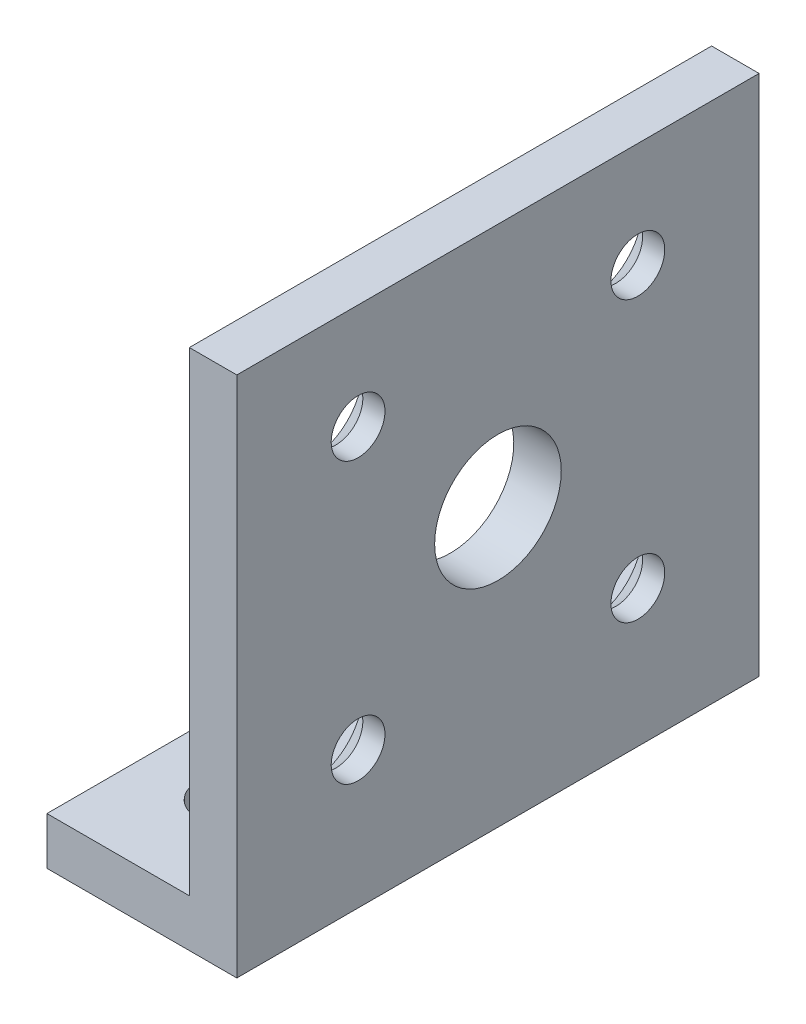
SolidWorks part; units mm, degrees
material "1060 合金"
ref_plane "前视基准面" through (0, 0, 0) normal (0, 0, 1) x (1, 0, 0)
ref_plane "上视基准面" through (0, 0, 0) normal (0, 1, 0) x (1, 0, 0)
ref_plane "右视基准面" through (0, 0, 0) normal (1, 0, 0) x (0, 0, -1)
sketch "草图1" plane through (0, 0, 0) normal (0, 0, 1) x (1, 0, 0)
  line L0 (0, 33) -> (0, 0)
  line L1 (0, 0) -> (-12, 0)
  dimension "D1" = 12
  dimension "D2" = 33
extrude "拉伸-薄壁1" add sketch "草图1" along normal mid plane 33 thin thin type one direction wall 3
sketch "草图4" plane through (-3, 0, 0) normal (-1, 0, 0) x (0, 0, 1)
  line L14 (16.5, 0) -> (-16.5, 0) construction
  line L15 (16.5, 0) -> (-16.5, 0) construction
  circle A0 centre (0, 17.5) radius 16.5 construction
  circle A1 centre (0, 17.5) radius 4
  dimension "D1" = 33
  dimension "D2" = 8
  dimension "D3" = 1
extrude "切除-拉伸1" cut sketch "草图4" against normal up to next
hole_wizard "打孔尺寸(%根据十字)槽半沉头木螺钉的类型2" positions "草图3" profile "草图2" countersink size "M3" standard "GB"
sketch "草图3" plane through (-3, 0, 0) normal (-1, 0, 0) x (0, 0, 1)
  line L1 (0, 17.5) -> (8.8388, 8.6612) construction
  line L3 (0, 17.5) -> (5.8968, 17.5) construction
  circle A0 centre (0, 17.5) radius 12.5
  circle A1 centre (0, 17.5) radius 4 construction
  point P6 (8.8388, 8.6612)
  point P38 (-8.8388, 8.6612)
  point P39 (-8.8388, 26.3388)
  point P40 (8.8388, 26.3388)
  dimension "D1" = 25
  dimension "D3" = 45
  dimension "D4" = 4
sketch "草图2" plane through (-3, 8.6612, 8.8388) normal (0, 1, 0) x (0, 0, 1)
  line L0 (0, 0) -> (0, 11.0215)
  line L1 (0, 11.0215) -> (1.7, 10)
  line L2 (1.7, 10) -> (1.7, 1.6)
  line L3 (1.7, 1.6) -> (3.3, 0)
  line L5 (3.3, 0) -> (0, 0)
  line L6 (-1.7, 1.6) -> (-3.3, 0) construction
  line L10 (0, 11.0215) -> (-1.7, 10) construction
  line L11 (0, -6.35) -> (0, 107.95) construction
  dimension "孔直径" = 3.4
  dimension "孔深度" = 10
  dimension "近端锥形沉头孔直径" = 6.6
  dimension "近端锥形沉头孔角度" = 90
  dimension "导头角度" = 118
hole_wizard "M4 螺纹孔1" positions "草图7" profile "草图6" tap size "M4" standard "GB" end condition up to next
sketch "草图7" plane through (0, 3, 0) normal (0, 1, 0) x (1, 0, 0)
  line L0 (0, 0) -> (-18.9251, 0) construction
  line L3 (-12, -16.5) -> (-12, 16.5) construction
  point P0 (-7, 10)
  point P12 (-7, -10)
  dimension "D1" = 20
  dimension "D2" = 5
sketch "草图6" plane through (-7, 3, -10) normal (1, 0, 0) x (0, 0, 1)
  line L0 (0, 0) -> (0, 3)
  line L1 (0, 3) -> (2, 3)
  line L2 (2, 3) -> (2, 0)
  line L5 (2, 0) -> (0, 0)
  line L11 (0, -6.35) -> (0, 107.95) construction
  dimension "螺纹线主直径" = 4
  dimension "通孔螺纹孔钻头深度" = 3
move or copy body "实体-移动/复制1" [suppressed] bodies to move or copy 109
